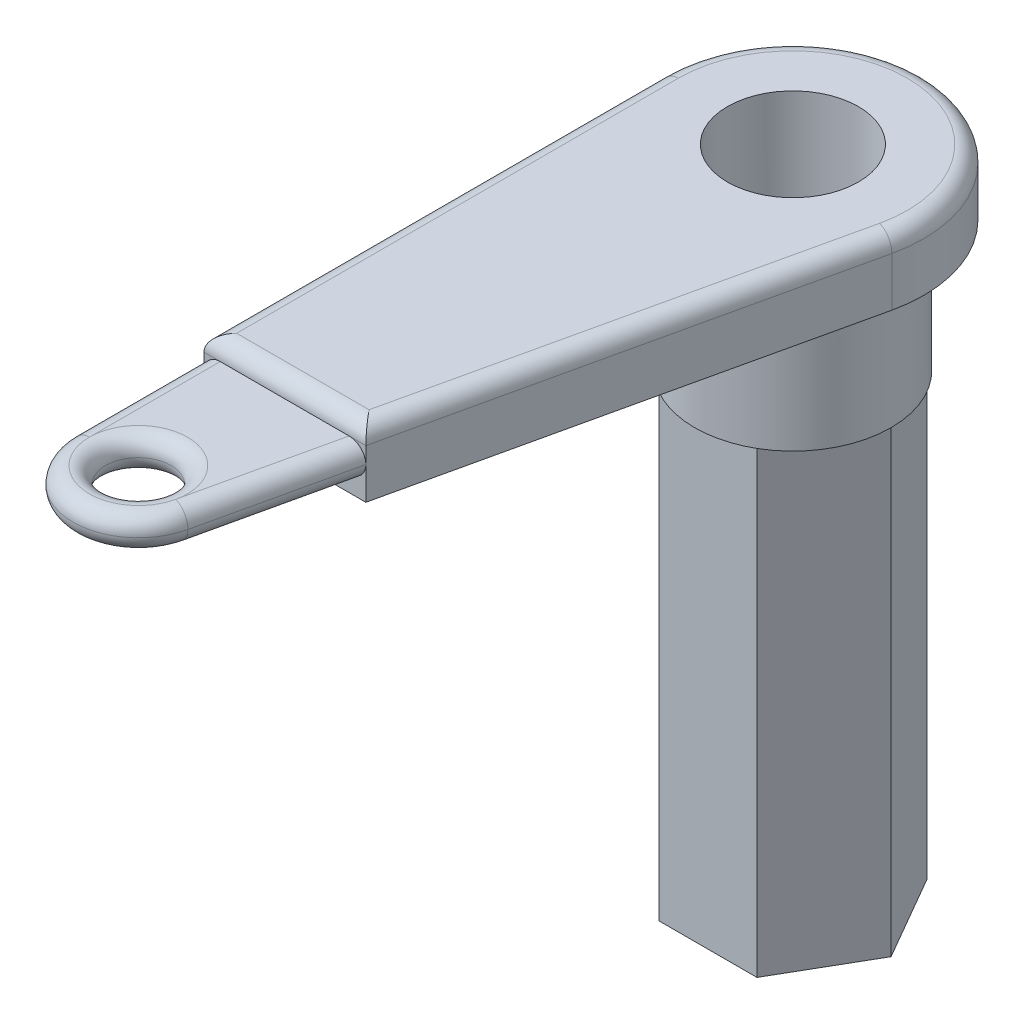
SolidWorks part; units mm, degrees
ref_plane "Front Plane" through (0, 0, 0) normal (0, 0, 1) x (1, 0, 0)
ref_plane "Top Plane" through (0, 0, 0) normal (0, 1, 0) x (1, 0, 0)
ref_plane "Right Plane" through (0, 0, 0) normal (1, 0, 0) x (0, 0, -1)
sketch "Sketch1" plane through (0, 0, 0) normal (0, 1, 0) x (1, 0, 0)
  line L0 (0, 20) -> (0, -100) construction
  line L1 (-20, 0) -> (-20, -90)
  line L2 (0, -90) -> (-20, -90) construction
  line L3 (19.5122, -4.3902) -> (-0.2439, -92.1951)
  arc A0 (19.5122, -4.3902) -> (-20, 0) centre (0, 0) ccw
  arc A1 (-20, -90) -> (-0.2439, -92.1951) centre (-10, -90) ccw
  circle A2 centre (-10, -90) radius 5
  circle A3 centre (0, 0) radius 10
  dimension "D1" = 40
  dimension "D4" = 20
  dimension "D3" = 10
  dimension "D2" = 120
extrude "Boss-Extrude1" add sketch "Sketch1" along normal blind 10
sketch "Sketch2" plane through (-20, 0, 0) normal (-1, 0, 0) x (0, 0, 1)
  line L0 (100, 5) -> (73.2627, 5) construction
  line L1 (100, 10) -> (70, 10)
  line L2 (100, 10) -> (100, 7.5)
  line L3 (100, 7.5) -> (70, 7.5)
  line L4 (70, 10) -> (70, 7.5)
  line L5 (100, 0) -> (100, 10) construction
  line L6 (100, 2.5) -> (70, 2.5)
  line L7 (70, 0) -> (70, 2.5)
  line L8 (100, 0) -> (70, 0)
  line L9 (100, 0) -> (100, 2.5)
  dimension "D1" = 2.5
  dimension "D2" = 30
extrude "Cut-Extrude1" cut sketch "Sketch2" against normal blind 30
fillet "Fillet1" radius 2.5 8 edges at (-20, 2.5, 80) (2.253, 2.5, 81.0976) (2.253, 7.5, 81.0976) (-11.1043, 7.5, 99.9388) (-10, 2.5, 95) (-11.1043, 2.5, 99.9388) (-20, 7.5, 80) (-10, 7.5, 85)
fillet "Fillet2" radius 2.5 4 edges at (12.1311, 10, 37.1951) (2.2086, 10, -19.8777) (-20, 10, 35) (-7.625, 10, 70)
sketch "Sketch3" plane through (0, 0, 0) normal (0, -1, 0) x (1, 0, 0)
  circle A0 centre (0, 0) radius 15
  circle A1 centre (0, 0) radius 10
extrude "Boss-Extrude2" add sketch "Sketch3" along normal blind 20
sketch "Sketch4" plane through (0, -20, 0) normal (0, -1, 0) x (-1, 0, 0)
  line L0 (0, 0) -> (15, 0) construction
  line L1 (15, 0) -> (7.5, 12.9904)
  line L2 (7.5, 12.9904) -> (-7.5, 12.9904)
  line L3 (-7.5, 12.9904) -> (-15, 0)
  line L4 (-15, 0) -> (-7.5, -12.9904)
  line L5 (-7.5, -12.9904) -> (7.5, -12.9904)
  line L6 (7.5, -12.9904) -> (15, 0)
  circle A0 centre (0, 0) radius 10
  circle A1 centre (0, 0) radius 12.9904 construction
  dimension "D1" = 15
extrude "Boss-Extrude3" add sketch "Sketch4" along normal blind 70
